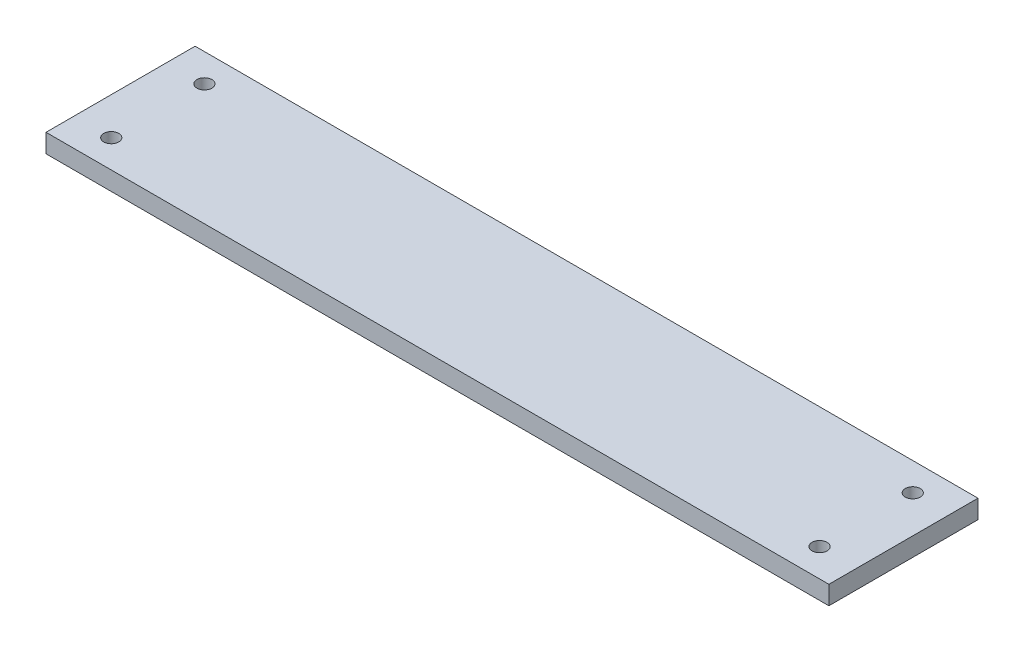
SolidWorks part; units mm, degrees
material "6061-T6 (SS)"
ref_plane "Front" through (0, 0, 0) normal (0, 0, 1) x (1, 0, 0)
ref_plane "Top" through (0, 0, 0) normal (0, 1, 0) x (1, 0, 0)
ref_plane "Right" through (0, 0, 0) normal (1, 0, 0) x (0, 0, -1)
sketch "Sketch1" plane through (0, 0, 0) normal (0, 1, 0) x (1, 0, 0)
  line L0 (266.7, 0) -> (266.7, 19.05) construction
  line L1 (0, 0) -> (266.7, 0)
  line L2 (0, 0) -> (0, 50.8)
  line L3 (0, 50.8) -> (266.7, 50.8)
  line L4 (266.7, 0) -> (266.7, 50.8)
  dimension "D1" = 50.8
extrude "Boss-Extrude1" add sketch "Sketch1" along normal blind 6.35
sketch "Sketch4" plane through (0, 6.35, 0) normal (0, 1, 0) x (1, 0, 0)
  line L0 (0, 0) -> (12.7, 9.525) construction
  line L1 (0, 0) -> (266.7, 0) construction
  line L6 (12.7, 9.525) -> (12.7, 41.275) construction
  line L7 (12.7, 41.275) -> (25.4, 50.8) construction
  line L8 (266.7, 50.8) -> (0, 50.8) construction
  line L9 (133.35, 0) -> (133.35, 19.6096) construction
  point P0 (12.7, 41.275)
  point P4 (12.7, 9.525)
  point P34 (254, 9.525)
  point P36 (254, 41.275)
  dimension "D1" = 31.75
  dimension "D2" = 25.4
hole_wizard "#10 Clearance Hole1" positions "Sketch4" profile "Sketch3" hole size "#10" standard "ANSI Inch" end condition up to next
sketch "Sketch3" plane through (12.7, 6.35, -41.275) normal (1, 0, 0) x (0, 0, 1)
  line L0 (0, 0) -> (0, 6.35)
  line L1 (0, 6.35) -> (2.5527, 6.35)
  line L2 (2.5527, 6.35) -> (2.5527, 0)
  line L5 (2.5527, 0) -> (0, 0)
  line L11 (0, -6.35) -> (0, 107.95) construction
  dimension "Thru Hole Dia." = 5.1054
  dimension "Thru Hole Depth" = 6.35
